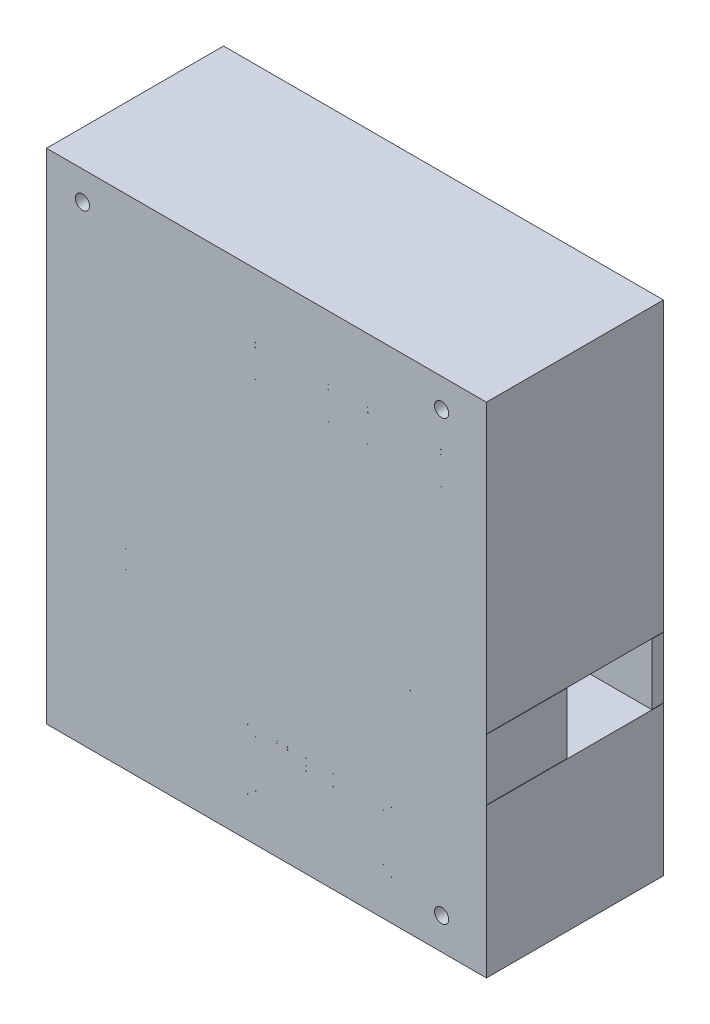
SolidWorks part; units mm, degrees
ref_plane "Front Plane" through (0, 0, 0) normal (0, 0, 1) x (1, 0, 0)
ref_plane "Top Plane" through (0, 0, 0) normal (0, 1, 0) x (1, 0, 0)
ref_plane "Right Plane" through (0, 0, 0) normal (1, 0, 0) x (0, 0, -1)
sketch "Placa Eagle" plane through (0, 0, 0) normal (0, 0, 1) x (1, 0, 0)
  line L0 (0, 0) -> (1524, 0)
  line L1 (1524, 0) -> (1524, 1752.6)
  line L2 (1524, 1752.6) -> (0, 1752.6)
  line L3 (0, 1752.6) -> (0, 0)
  line L4 (996.188, 1414.145) -> (738.124, 1414.145)
  line L5 (738.124, 1414.145) -> (738.124, 1510.919)
  line L6 (738.124, 1510.919) -> (738.124, 1527.048)
  line L7 (738.124, 1527.048) -> (996.188, 1527.048)
  line L8 (996.188, 1527.048) -> (996.188, 1510.919)
  line L9 (996.188, 1510.919) -> (996.188, 1414.145)
  line L10 (0, -10.668) -> (0, 0)
  line L11 (1394.46, 1414.145) -> (1136.396, 1414.145)
  line L12 (1136.396, 1414.145) -> (1136.396, 1510.919)
  line L13 (1136.396, 1510.919) -> (1136.396, 1527.048)
  line L14 (1136.396, 1527.048) -> (1394.46, 1527.048)
  line L15 (1394.46, 1527.048) -> (1394.46, 1510.919)
  line L16 (1394.46, 1510.919) -> (1394.46, 1414.145)
  line L17 (231.775, -10.668) -> (0, -10.668)
  line L18 (1524, -10.668) -> (1524, 0)
  line L19 (1286.002, 620.522) -> (1286.002, 518.922)
  line L20 (1286.002, 518.922) -> (1311.402, 518.922)
  line L21 (1420.622, 518.922) -> (1468.628, 518.922)
  line L22 (393.065, -10.668) -> (1524, -10.668)
  line L23 (1524, -10.668) -> (1555.242, -10.668)
  line L24 (1524, 1752.6) -> (1555.242, 1752.6)
  line L25 (1555.242, 520.2123) -> (1555.242, -10.668)
  line L26 (1555.242, 733.5317) -> (1555.242, 1752.6)
  line L27 (1397, 101.6) -> (1397, -10.668) construction
  line L28 (1397, 101.6) -> (1555.242, 101.6) construction
  line L29 (1397, 1651) -> (1524, 1651) construction
  line L30 (1397, 1752.6) -> (1397, 1651) construction
  line L31 (1397, 1651) -> (127, 1651) construction
  line L58 (1286.002, 734.822) -> (1286.002, 620.522)
  line L59 (1311.402, 518.922) -> (1420.622, 518.922)
  line L60 (1468.628, 518.922) -> (1555.242, 518.922)
  line L61 (1555.242, 734.822) -> (1286.002, 734.822)
  line L62 (1555.242, 518.922) -> (1555.242, 734.822)
  line L286 (231.775, 21.59) -> (231.775, 215.138)
  line L287 (231.775, 215.138) -> (393.065, 215.138)
  line L288 (393.065, 215.138) -> (393.065, 21.59)
  line L289 (231.775, 21.59) -> (231.775, -10.668)
  line L290 (231.775, -10.668) -> (393.065, -10.668)
  line L291 (393.065, -10.668) -> (393.065, 21.59)
  line L292 (376.936, 602.234) -> (376.936, 666.75)
  line L293 (376.936, 666.75) -> (280.162, 666.75)
  line L294 (280.162, 666.75) -> (280.162, 602.234)
  line L295 (280.162, 602.234) -> (376.936, 602.234)
  line L350 (1219.454, 130.556) -> (711.454, 130.556)
  line L351 (711.454, 130.556) -> (711.454, 343.916)
  line L352 (711.454, 343.916) -> (814.6288, 343.916)
  line L353 (814.6288, 343.916) -> (814.6288, 336.296)
  line L354 (814.6288, 336.296) -> (852.1954, 336.296)
  line L355 (852.1954, 336.296) -> (852.1954, 343.916)
  line L356 (852.1954, 343.916) -> (917.6258, 343.916)
  line L357 (917.6258, 343.916) -> (917.6258, 304.546)
  line L358 (917.6258, 304.546) -> (1013.2822, 304.546)
  line L359 (1013.2822, 304.546) -> (1013.2822, 343.916)
  line L360 (917.6258, 343.916) -> (1013.2822, 343.916)
  line L361 (1013.2822, 343.916) -> (1219.454, 343.916)
  line L362 (1219.454, 343.916) -> (1219.454, 130.556)
  line L363 (1190.879, 154.051) -> (740.029, 154.051)
  line L364 (740.029, 154.051) -> (740.029, 320.421)
  line L365 (740.029, 320.421) -> (917.6258, 320.421)
  line L366 (1013.2822, 320.421) -> (1190.879, 320.421)
  line L367 (1190.879, 320.421) -> (1190.879, 154.051)
  circle A0 centre (127, 1651) radius 25.07
  circle A1 centre (1397, 1651) radius 25.07
  circle A2 centre (1397, 101.6) radius 25.07
  arc A3 (738.124, 1415.4353) -> (739.4143, 1414.145) centre (738.124, 1414.145) ccw
  arc A4 (994.8977, 1414.145) -> (996.188, 1415.4353) centre (996.188, 1414.145) ccw
  circle A5 centre (738.124, 1510.919) radius 1.2903
  arc A6 (739.4143, 1527.048) -> (738.124, 1525.7577) centre (738.124, 1527.048) ccw
  arc A7 (996.188, 1525.7577) -> (994.8977, 1527.048) centre (996.188, 1527.048) ccw
  circle A8 centre (996.188, 1510.919) radius 1.2903
  arc A9 (1136.396, 1415.4353) -> (1137.6863, 1414.145) centre (1136.396, 1414.145) ccw
  arc A10 (1393.1697, 1414.145) -> (1394.46, 1415.4353) centre (1394.46, 1414.145) ccw
  circle A11 centre (1136.396, 1510.919) radius 1.2903
  arc A12 (1137.6863, 1527.048) -> (1136.396, 1525.7577) centre (1136.396, 1527.048) ccw
  arc A13 (1394.46, 1525.7577) -> (1393.1697, 1527.048) centre (1394.46, 1527.048) ccw
  circle A14 centre (1394.46, 1510.919) radius 1.2903
  arc A15 (1287.2923, 734.822) -> (1286.002, 733.5317) centre (1286.002, 734.822) ccw
  arc A16 (1553.9517, 518.922) -> (1555.242, 520.2123) centre (1555.242, 518.922) ccw
  arc A17 (1555.242, 733.5317) -> (1553.9517, 734.822) centre (1555.242, 734.822) ccw
  arc A23 (711.454, 131.8463) -> (712.7443, 130.556) centre (711.454, 130.556) ccw
  arc A24 (1218.1637, 130.556) -> (1219.454, 131.8463) centre (1219.454, 130.556) ccw
  arc A25 (712.7443, 343.916) -> (711.454, 342.6257) centre (711.454, 343.916) ccw
  arc A26 (814.6288, 342.6257) -> (813.3385, 343.916) centre (814.6288, 343.916) ccw
  arc A27 (814.6288, 337.5863) -> (815.9191, 336.296) centre (814.6288, 336.296) ccw
  arc A28 (850.9051, 336.296) -> (852.1954, 337.5863) centre (852.1954, 336.296) ccw
  arc A29 (853.4857, 343.916) -> (852.1954, 342.6257) centre (852.1954, 343.916) ccw
  circle A30 centre (917.6258, 343.916) radius 1.2903
  arc A31 (917.6258, 305.8363) -> (918.9161, 304.546) centre (917.6258, 304.546) ccw
  arc A32 (1011.9919, 304.546) -> (1013.2822, 305.8363) centre (1013.2822, 304.546) ccw
  circle A33 centre (1013.2822, 343.916) radius 1.2903
  arc A34 (1219.454, 342.6257) -> (1218.1637, 343.916) centre (1219.454, 343.916) ccw
  arc A35 (740.029, 155.3413) -> (741.3193, 154.051) centre (740.029, 154.051) ccw
  arc A37 (1189.5887, 154.051) -> (1190.879, 155.3413) centre (1190.879, 154.051) ccw
  arc A39 (741.3193, 320.421) -> (740.029, 319.1307) centre (740.029, 320.421) ccw
  arc A40 (1190.879, 319.1307) -> (1189.5887, 320.421) centre (1190.879, 320.421) ccw
  arc A131 (1284.7117, 620.522) -> (1287.2923, 620.522) centre (1286.002, 620.522) ccw
  arc A133 (1420.622, 517.6317) -> (1420.622, 520.2123) centre (1420.622, 518.922) ccw
  arc A134 (1311.402, 520.2123) -> (1311.402, 517.6317) centre (1311.402, 518.922) ccw
  arc A136 (1468.628, 520.2123) -> (1468.628, 517.6317) centre (1468.628, 518.922) ccw
  arc A141 (1553.9517, 733.552) -> (1556.5323, 733.552) centre (1555.242, 733.552) ccw
  arc A603 (377.7437, 666.75) -> (376.1283, 666.75) centre (376.936, 666.75) ccw
  arc A604 (376.1283, 602.234) -> (377.7437, 602.234) centre (376.936, 602.234) ccw
  arc A605 (280.162, 667.5552) -> (280.162, 665.9448) centre (280.162, 666.75) ccw
  arc A606 (376.936, 665.9448) -> (376.936, 667.5552) centre (376.936, 666.75) ccw
  arc A607 (279.3568, 602.234) -> (280.9697, 602.234) centre (280.1633, 602.234) ccw
  arc A608 (280.9697, 666.75) -> (279.3568, 666.75) centre (280.1633, 666.75) ccw
  arc A609 (376.936, 601.4288) -> (376.936, 603.0392) centre (376.936, 602.234) ccw
  arc A610 (280.162, 603.0392) -> (280.162, 601.4288) centre (280.162, 602.234) ccw
  arc A812 (917.6258, 319.1307) -> (917.6258, 321.7113) centre (917.6258, 320.421) ccw
  arc A815 (1013.2822, 321.7113) -> (1013.2822, 319.1307) centre (1013.2822, 320.421) ccw
  circle A819 centre (1094.486, 269.494) radius 11.43
  circle A821 centre (1094.486, 204.978) radius 11.43
  circle A823 centre (1029.97, 269.494) radius 11.43
  circle A825 centre (1029.97, 204.978) radius 11.43
  circle A827 centre (965.454, 269.494) radius 11.43
  circle A829 centre (965.454, 204.978) radius 11.43
  circle A831 centre (900.938, 269.494) radius 11.43
  circle A833 centre (900.938, 204.978) radius 11.43
  circle A835 centre (836.422, 269.494) radius 11.43
  circle A837 centre (836.422, 204.978) radius 11.43
sketch "Sketch2" plane through (0, 0, 0) normal (0, 1, 0) x (1, 0, 0)
  line L0 (1219.4513, -253.4761) -> (711.4513, -253.4761)
  line L1 (814.6261, -40.1161) -> (852.1927, -40.1161)
  line L3 (231.7727, -376.05) -> (393.0659, -376.05)
  line L4 (231.7727, -376.05) -> (393.0659, -376.05)
  line L5 (231.7727, -376.05) -> (231.7727, -526.47)
  line L8 (393.0659, -376.05) -> (393.0659, -526.47)
  line L10 (231.7727, -526.47) -> (393.0659, -526.47)
  line L11 (393.0659, -376.05) -> (393.0659, -526.47)
  line L12 (231.7727, -376.05) -> (393.0659, -526.47) construction
  line L13 (393.0659, -376.05) -> (231.7727, -526.47) construction
  line L14 (711.4513, -253.4761) -> (711.4513, -40.1161)
  line L15 (711.4513, -40.1161) -> (814.6261, -40.1161)
  line L19 (852.1927, -40.1161) -> (917.6231, -40.1161)
  line L23 (917.6231, -40.1161) -> (1013.2795, -40.1161)
  line L24 (1013.2795, -40.1161) -> (1219.4513, -40.1161)
  line L25 (1219.4513, -40.1161) -> (1219.4513, -253.4761)
  point P17 (312.4193, -451.26)
extrude "Boss-Extrude2" add sketch "Placa Eagle" along normal blind 625.925 contours A835 | A831 | A837 | A833 | A827 | A829 | A823 | A825 | A819 | A821 | A32 L358 A31 L357 L365 L364 L363 L367 L366 L359 A837 A835 A833 A831 A829 A827 A825 A823 A821 A819 | A815 L359 A33 L360 A30 L357 A812 L358 | A40 L367 A37 L363 A35 L364 A39 L365 L357 A30 L356 L355 A28 L354 A27 L353 L352 L351 L350 L362 L361 A33 L359 L366 | A15 L61 L1 L2 L3 L0 L289 L286 L287 L288 L291 L60 L21 L59 L20 L19 L58 A610 L294 A605 A608 L293 L292 L295 | L25 L62 L26 L61 L1 L60 | L1 L61 L58 L19 L20 L59 L21 L60 | A16 L60 L1 L18 L23 L25 | A17 L26 L24 L1 L61 | A8 L8 L7 L6 A5 L5 L4 L9 | A14 L15 L14 L13 A11 L12 L11 L16 | L0 L291 L288 L287 L286 L289 | L294 L295 L292 L293 | L290 L291 L0 L289 | L289 L0 L10 L17 | L291 L22 L18 L0 region at (738.8236, 907.0306, 0) region at (115.8875, -5.334, 0) region at (312.42, 107.569, 0) region at (312.42, -5.334, 0) region at (958.5325, -5.334, 0) region at (1539.6204, 1243.7319, 0) region at (1539.6198, 254.1061, 0) region at (1539.621, 626.872, 0) region at (1405.001, 626.872, 0) region at (867.156, 1470.5893, 0) region at (1265.428, 1470.5893, 0) region at (328.549, 634.492, 0) region at (1218.8088, 136.0659, 0) region at (965.454, 324.223, 0) region at (965.454, 235.5814, 0) region at (1094.486, 269.494, 0) region at (1094.486, 204.978, 0) region at (1029.97, 269.494, 0) region at (1029.97, 204.978, 0) region at (965.454, 269.494, 0) region at (965.454, 204.978, 0) region at (900.938, 269.494, 0) region at (900.938, 204.978, 0) region at (836.422, 269.494, 0) region at (836.422, 204.978, 0)
extrude "Cut-Extrude2" cut sketch "Sketch2" along normal blind 867.925 and the other way blind 6230 contours L25 L24 L23 L19 L1 L15 L14 L0 | L5 L10 L8 L3 region at (965.4513, 0, 146.7961) region at (312.4193, 0, 451.26)
sketch "Sketch11" plane through (0, 0, 0) normal (1, 0, 0) x (0, 0, -1)
  line L1 (-40.112, 626.872) -> (-40.112, 736.1123)
  line L2 (-40.112, 626.872) -> (-40.112, 517.6317)
  line L3 (-40.112, 736.1123) -> (-193.1946, 736.1123)
  line L5 (-340.952, 626.872) -> (-340.952, 736.1123)
  line L6 (-340.952, 736.1123) -> (-193.1946, 736.1123)
  line L7 (-625.925, 517.6317) -> (0, 517.6317) construction
  line L8 (-40.112, 517.6317) -> (-340.952, 517.6317)
  line L9 (-340.952, 517.6317) -> (-340.952, 626.872)
extrude "Cut-Extrude3" cut sketch "Sketch11" along normal blind 1935.925 and the other way blind 20
extrude "Boss-Extrude3" add sketch "Sketch11<2>" along normal blind 507.925
sketch "Sketch11<2>" plane through (0, 0, 0) normal (1, 0, 0) x (0, 0, -1) same geometry as "Sketch11"
scale "Scale2" scale about centroid uniform scaling yes scale factor 0.039888
